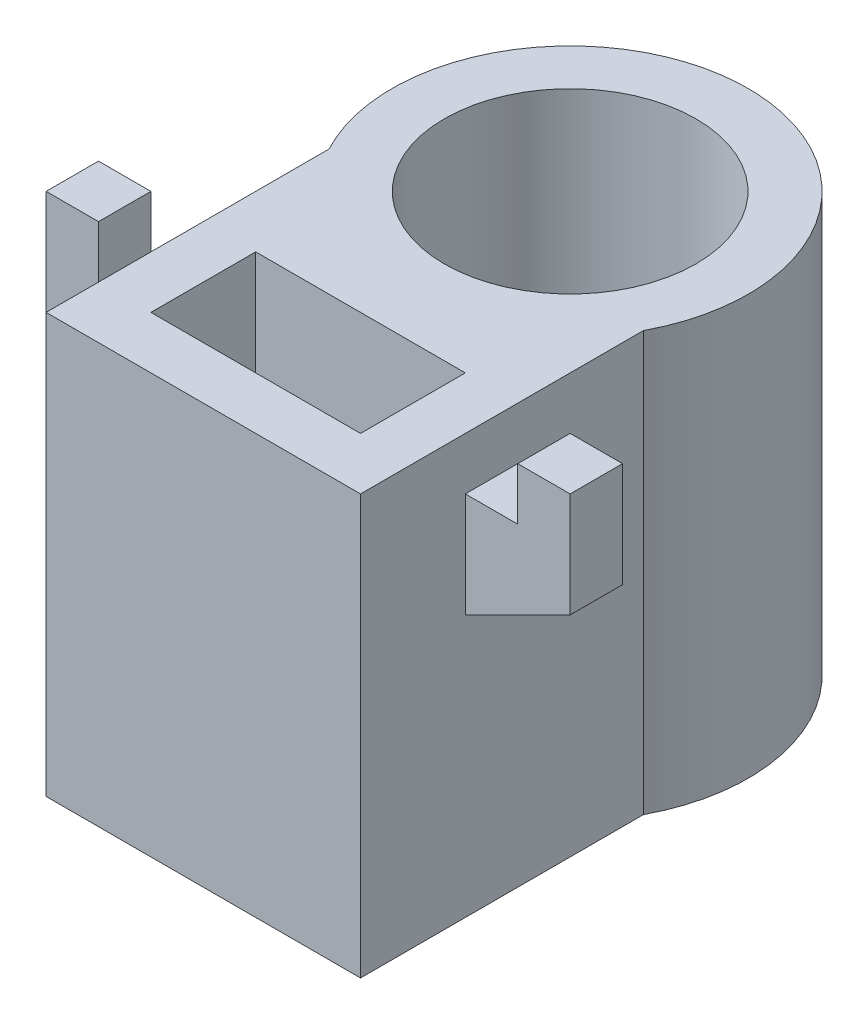
SolidWorks part; units mm, degrees
ref_plane "Front Plane" through (0, 0, 0) normal (0, 0, 1) x (1, 0, 0)
ref_plane "Top Plane" through (0, 0, 0) normal (0, 1, 0) x (1, 0, 0)
ref_plane "Right Plane" through (0, 0, 0) normal (1, 0, 0) x (0, 0, -1)
sketch "Sketch1" plane through (0, 0, 0) normal (0, 1, 0) x (1, 0, 0)
  line L1 (-6.35, -19.05) -> (6.35, -19.05)
  line L2 (-6.35, -19.05) -> (-6.35, -12.7)
  line L3 (-6.35, -12.7) -> (6.35, -12.7)
  line L4 (6.35, -19.05) -> (6.35, -12.7)
  line L7 (-9.525, -22.225) -> (9.525, -22.225)
  line L8 (-9.525, -22.225) -> (-9.525, -5.08)
  line L10 (9.525, -22.225) -> (9.525, -5.08)
  circle A0 centre (0, 0) radius 7.62
  arc A1 (9.525, -5.08) -> (-9.525, -5.08) centre (0, 0) ccw
  point P3 (0, -12.7)
  point P8 (0, -22.225)
  dimension "D5" = 3.175
  dimension "D6" = 3.175
  dimension "D3" = 15.24
  dimension "D7" = 12.7
  dimension "D1" = 6.35
  dimension "D2" = 12.7
  dimension "D4" = 3.175
extrude "Boss-Extrude1" add sketch "Sketch1" along normal blind 25.4
ref_plane "Plane1" through (0, 0, 0) normal (1, 0, 0) x (0, 0, -1)
ref_plane "Plane2" through (0, 0, 15.875) normal (0, 0, -1) x (-1, 0, 0)
sketch "Sketch3" plane through (0, 0, 15.875) normal (0, 0, -1) x (-1, 0, 0)
  line L0 (9.525, 25.4) -> (-9.525, 25.4) construction
  line L1 (-9.525, 22.225) -> (-9.525, 15.875)
  line L2 (-12.7, 22.225) -> (-12.7, 25.4)
  line L3 (-12.7, 25.4) -> (-15.875, 25.4)
  line L4 (-15.875, 19.05) -> (-15.875, 25.4)
  line L5 (-12.7, 22.225) -> (-9.525, 22.225)
  line L6 (-15.875, 19.05) -> (-9.525, 15.875)
  line L7 (-9.525, 25.4) -> (-9.525, 0) construction
  dimension "D1" = 3.175
  dimension "D2" = 3.175
  dimension "D3" = 3.175
  dimension "D4" = 3.175
  dimension "D5" = 6.35
extrude "Boss-Extrude2" add sketch "Sketch3" along normal blind 3.175
mirror "Mirror1" about plane through (0, 0, 0) normal (1, 0, 0) of "Boss-Extrude2"
